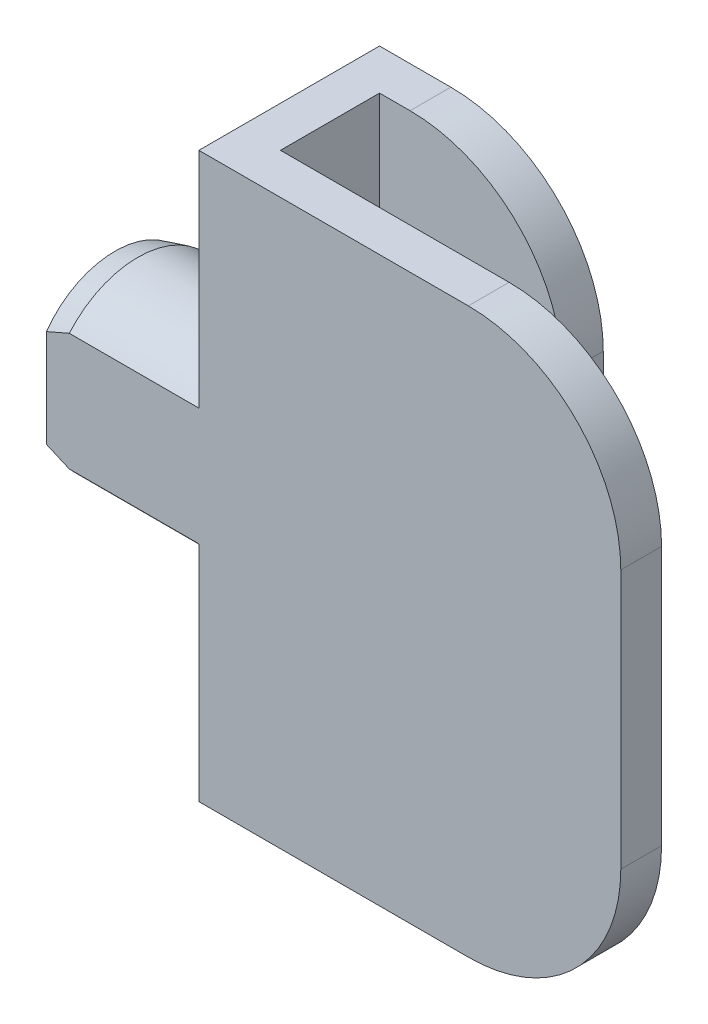
SolidWorks part; units mm, degrees
ref_plane "Front Plane" through (0, 0, 0) normal (0, 0, 1) x (1, 0, 0)
ref_plane "Top Plane" through (0, 0, 0) normal (0, 1, 0) x (1, 0, 0)
ref_plane "Right Plane" through (0, 0, 0) normal (1, 0, 0) x (0, 0, -1)
sketch "Sketch2" plane through (0, 0, 0) normal (0, 1, 0) x (1, 0, 0)
  line L0 (12, 3.25) -> (0, 3.25)
  line L1 (0, 3.25) -> (0, -3.25)
  line L2 (0, -3.25) -> (25, -3.25)
  line L3 (12, 5.925) -> (-2.675, 5.925)
  line L4 (-2.675, 5.925) -> (-2.675, -5.925)
  line L5 (-2.675, -5.925) -> (25, -5.925)
  line L6 (12, 3.25) -> (12, 5.925)
  line L7 (25, -3.25) -> (25, -5.925)
  point P3 (0, 0)
  dimension "D1" = 6.5
  dimension "D2" = 12
  dimension "D3" = 25
  dimension "D4" = 11.85
extrude "Boss-Extrude1" add sketch "Sketch2" along normal mid plane 37
sketch "Sketch3" plane through (-2.675, 0, 0) normal (-1, 0, 0) x (0, 0, 1)
  circle A0 centre (1.425, 0) radius 5.925
  dimension "D1" = 11.85
  dimension "D2" = 1.425
extrude "Boss-Extrude2" add sketch "Sketch3" along normal blind 10
sketch "Sketch5" plane through (0, 18.5, 0) normal (0, 1, 0) x (1, 0, 0)
  line L1 (-2.675, -5.925) -> (-16.5713, -5.925)
  line L2 (-2.675, -5.925) -> (-2.675, -9.2955)
  line L3 (-2.675, -9.2955) -> (-16.5713, -9.2955)
  line L4 (-16.5713, -5.925) -> (-16.5713, -9.2955)
extrude "Cut-Extrude2" cut sketch "Sketch5" against normal through all
chamfer "Chamfer1" distance 1.5 angle 15 1 edges at (-12.675, 0, -4.5) first distance on face at (-7.675, 0, 0.7125)
sketch "Sketch7" plane through (0, 0, -5.925) normal (0, 0, -1) x (-1, 0, 0)
  line L0 (-12, 18.5) -> (2.675, 18.5) construction
  line L1 (-3.5, 18.5) -> (-12, 18.5)
  line L2 (-3.5, 18.5) -> (-3.5, 17.35)
  line L3 (-3.5, 17.35) -> (-12, 17.35)
  line L4 (-12, 18.5) -> (-12, 17.35)
  line L5 (-12, 18.5) -> (-12, -18.5) construction
  line L6 (0, 0) -> (-6.7973, 0) construction
  line L7 (-12, -18.5) -> (-12, -17.35)
  line L8 (-3.5, -17.35) -> (-12, -17.35)
  line L9 (-3.5, -18.5) -> (-3.5, -17.35)
  line L10 (-3.5, -18.5) -> (-12, -18.5)
  line M3 (-12, -18.5) -> (2.675, -18.5)
  line M6 (-12, 18.5) -> (-12, -18.5)
  dimension "D1" = 1.15
  dimension "D2" = 8.5
extrude "Cut-Extrude4" cut sketch "Sketch7" against normal up to next contours L9 L8 M3 M6 region at (7.75, -17.925, -5.925)
sketch "Sketch9" plane through (0, 0, -3.25) normal (0, 0, 1) x (1, 0, 0)
  line L0 (12, 18.5) -> (12, -17.35) construction
  line L1 (-2.675, -18.5) -> (12, -18.5)
  line L2 (-2.675, -18.5) -> (-2.675, -20)
  line L3 (-2.675, -20) -> (12, -20)
  line L4 (12, -18.5) -> (12, -20)
  line L5 (3.5, -17.35) -> (12, -17.35) construction
  line L6 (11, -17.35) -> (10, -17.35)
  line L7 (3.5, -18.5) -> (3.5, -17.35) construction
  arc A0 (11, -17.35) -> (10, -17.35) centre (10.5, -17.35) cw
  dimension "D2" = 0.5
  dimension "D1" = 1.5
  dimension "D3" = 7
extrude "Boss-Extrude5" add sketch "Sketch9" against normal blind 1.8
fillet "Fillet8" radius 1.5 1 edges at (-1.3375, -18.5, -3.25)
sketch "Sketch10" plane through (0, 0, -5.05) normal (0, 0, -1) x (-1, 0, 0)
  line L1 (2.675, -20) -> (0, -20)
  line L2 (2.675, -20) -> (2.675, -18.5)
  line L3 (2.675, -18.5) -> (0, -18.5)
  line L4 (0, -20) -> (0, -18.5)
  line L6 (-3.5, -18.5) -> (2.675, -18.5) construction
  line L7 (2.675, -20) -> (-12, -20) construction
  line L8 (0, -26.8697) -> (0, -4.0055) construction
extrude "Boss-Extrude6" add sketch "Sketch10" along normal up to surface (0.875 mm away) up to face at (4.275, -5.7833, -5.925)
fillet "Fillet9" radius 10 1 edges at (0, -19.25, -5.05)
fillet "Fillet10" radius 10 3 edges at (25, -18.5, 4.5875) (25, 18.5, 4.5875) (12, 18.5, -4.5875)
